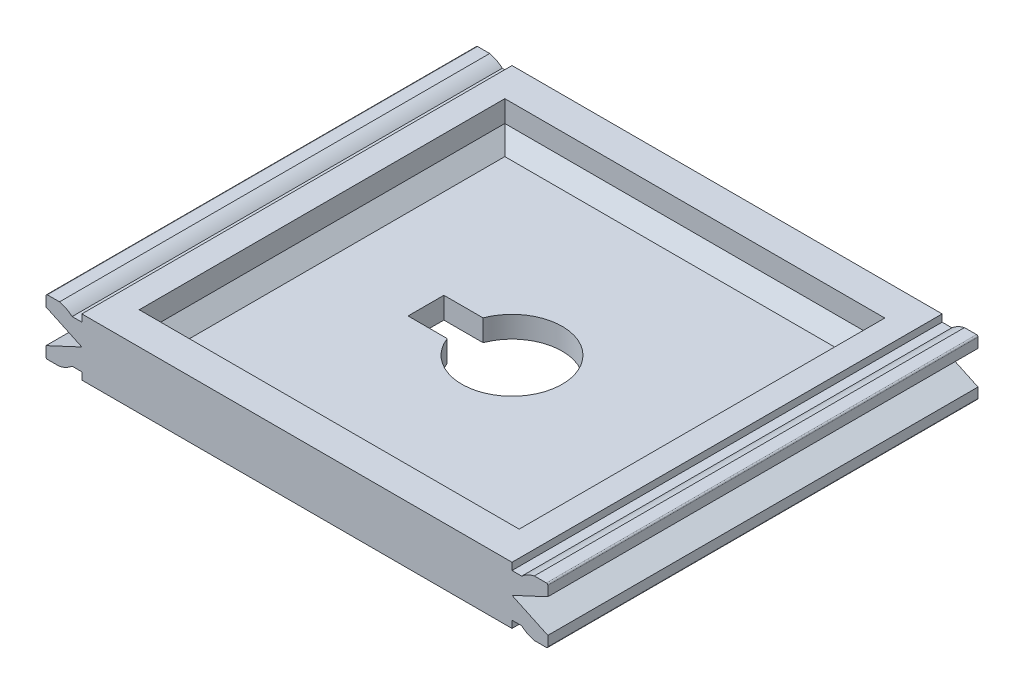
SolidWorks part; units mm, degrees
ref_plane "前视基准面" through (0, 0, 0) normal (0, 0, 1) x (1, 0, 0)
ref_plane "上视基准面" through (0, 0, 0) normal (0, 1, 0) x (1, 0, 0)
ref_plane "右视基准面" through (0, 0, 0) normal (1, 0, 0) x (0, 0, -1)
sketch "草图1" plane through (0, 0, 0) normal (0, 1, 0) x (1, 0, 0)
  line L0 (15, 15) -> (15, -15)
  line L1 (15, 15) -> (-15, 15)
  line L2 (15, -15) -> (-15, -15)
  line L3 (-15, 15) -> (-15, -15)
  line L4 (15, 15) -> (-15, -15) construction
  line L5 (15, -15) -> (-15, 15) construction
  point P1 (0, 0)
  dimension "D1" = 30
  dimension "D2" = 30
extrude "凸台-拉伸1" add sketch "草图1" along normal blind 2 and the other way blind 2
sketch "草图2" plane through (0, 2, 0) normal (0, 1, 0) x (1, 0, 0)
  line L0 (13.25, 12.75) -> (13.25, -12.75)
  line L1 (13.25, 12.75) -> (-13.25, 12.75)
  line L2 (13.25, -12.75) -> (-13.25, -12.75)
  line L3 (-13.25, 12.75) -> (-13.25, -12.75)
  line L4 (13.25, 12.75) -> (-13.25, -12.75) construction
  line L5 (13.25, -12.75) -> (-13.25, 12.75) construction
  point P1 (0, 0)
  dimension "D1" = 25.5
  dimension "D2" = 26.5
extrude "切除-拉伸1" cut sketch "草图2" against normal blind 2.5
chamfer "倒角1" distance 1 angle 45 4 edges at (13.25, -0.5, 0) (0, -0.5, 12.75) (-13.25, -0.5, 0) (0, -0.5, -12.75)
sketch "草图3" plane through (0, 0, 0) normal (0, 0, 1) x (1, 0, 0)
  line L0 (15, 0) -> (17, 0) construction
  line L1 (15, -2) -> (15, 2) construction
  line L2 (17, 0) -> (17.5, 0) construction
  line L3 (15, 1.5) -> (15, 0)
  line L4 (15, 1.5) -> (15.6771, 1.5)
  line L5 (17.5, 1.1658) -> (17.5, 1.95)
  line L6 (17.5, 1.95) -> (16.5556, 1.95)
  line L7 (15, 0) -> (17.5, 1.1658)
  arc A0 (16.5556, 1.95) -> (15.6771, 1.5) centre (17, 0) ccw
  dimension "D5" = 2
  dimension "D1" = 2
  dimension "D2" = 0.5
  dimension "D3" = 1.5
  dimension "D4" = 1.95
  dimension "D6" = 25
  dimension "D7" = 1.1658
extrude "凸台-拉伸2" add sketch "草图3" along normal blind 15 and the other way blind 15 contours L6 A0 L4 L7 L5 region at (16.1553, 1.1423, 0)
mirror "镜向1" about plane through (0, 0, 0) normal (0, 1, 0) of "凸台-拉伸2"
mirror "镜向2" about plane through (0, 0, 0) normal (1, 0, 0) of "镜向1", "凸台-拉伸2"
fillet "圆角1" radius 0.1 4 edges at (17.5, -1.95, 0) (17.5, 1.95, 0) (-17.5, -1.95, 0) (-17.5, 1.95, 0)
sketch "草图4" plane through (0, -0.5, 0) normal (0, 1, 0) x (1, 0, 0)
  line L0 (0, 0) -> (-6, 0) construction
  line L1 (-3.2692, 1.25) -> (-6, 1.25)
  line L2 (-3.2692, -1.25) -> (-6, -1.25)
  line L3 (-6, 1.25) -> (-6, -1.25)
  line L5 (0, 1.25) -> (-6, 1.25) construction
  line L6 (0, -1.25) -> (-6, -1.25) construction
  arc A0 (-3.2692, -1.25) -> (-3.2692, 1.25) centre (0, 0) ccw
  dimension "D1" = 7
  dimension "D2" = 6
  dimension "D3" = 1.25
  dimension "D4" = 1.25
extrude "切除-拉伸2" cut sketch "草图4" against normal up to next
